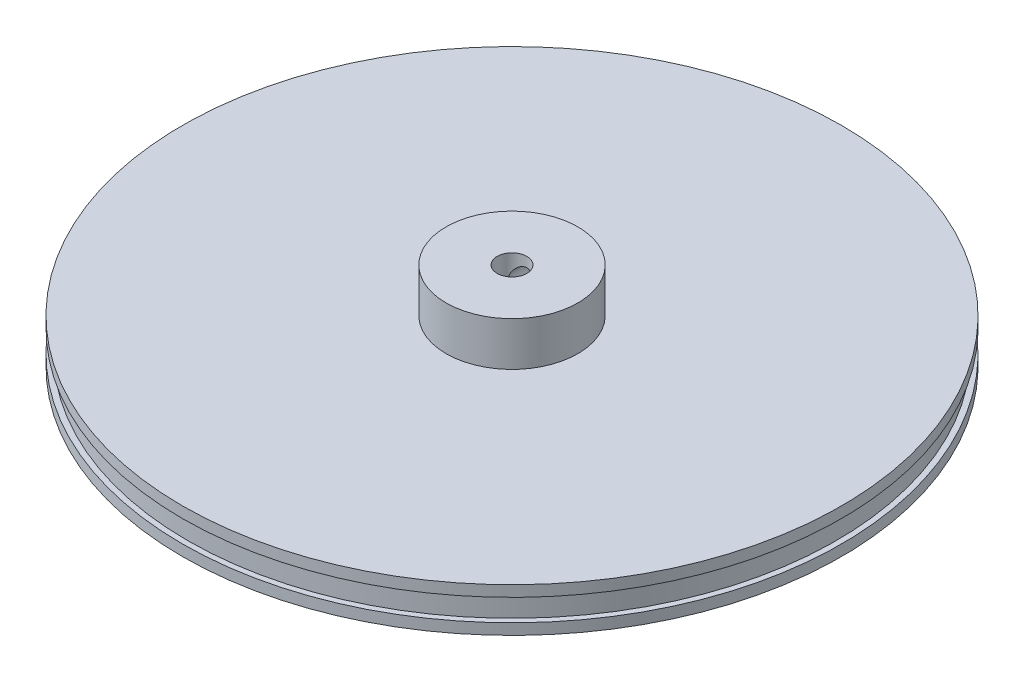
SolidWorks part; units mm, degrees
ref_plane "Front Plane" through (0, 0, 0) normal (0, 0, 1) x (1, 0, 0)
ref_plane "Top Plane" through (0, 0, 0) normal (0, 1, 0) x (1, 0, 0)
ref_plane "Right Plane" through (0, 0, 0) normal (1, 0, 0) x (0, 0, -1)
sketch "Sketch1" plane through (0, 0, 0) normal (0, 1, 0) x (1, 0, 0)
  circle A0 centre (0, 0) radius 30
  circle A1 centre (0, 0) radius 6
  circle A2 centre (0, 0) radius 1.35
  dimension "D1" = 2.7
  dimension "D2" = 60
  dimension "D3" = 12
extrude "Boss-Extrude1" add sketch "Sketch1" along normal blind 4 contours A2 | A0 region at (0, 0, 0)
extrude "Boss-Extrude2" add sketch "Sketch1<3>" along normal blind 8 contours A1 A2 region at (-5.8303, 0, 0)
sketch "Sketch1<3>" plane through (0, 0, 0) normal (0, 1, 0) x (1, 0, 0) same geometry as "Sketch1"
sketch "Sketch2" plane through (0, 0, 0) normal (0, 0, 1) x (1, 0, 0)
  line L0 (30, 0) -> (30, 4) construction
  line L1 (30, 3) -> (29.5, 3)
  line L2 (30, 3) -> (30, 1)
  line L3 (30, 1) -> (29.5, 1)
  line L4 (29.5, 3) -> (29.5, 1)
  line L5 (30, 4) -> (-30, 4) construction
  line L6 (-30, 0) -> (30, 0) construction
  dimension "D1" = 1
  dimension "D2" = 1
  dimension "D3" = 0.5
revolve "Cut-Revolve1" cut sketch "Sketch2" angle 360 about axis through (0, 4, 0) along (0, -1, 0)
sketch "Sketch3" plane through (0, 0, 0) normal (0, 0, 1) x (1, 0, 0)
  line L0 (0, 8) -> (0, 0) construction
  line L1 (6, 8) -> (-6, 8) construction
  circle A0 centre (0, 6) radius 1.1
  dimension "D1" = 2.2
  dimension "D2" = 2
extrude "Cut-Extrude1" cut sketch "Sketch3" against normal blind 10
